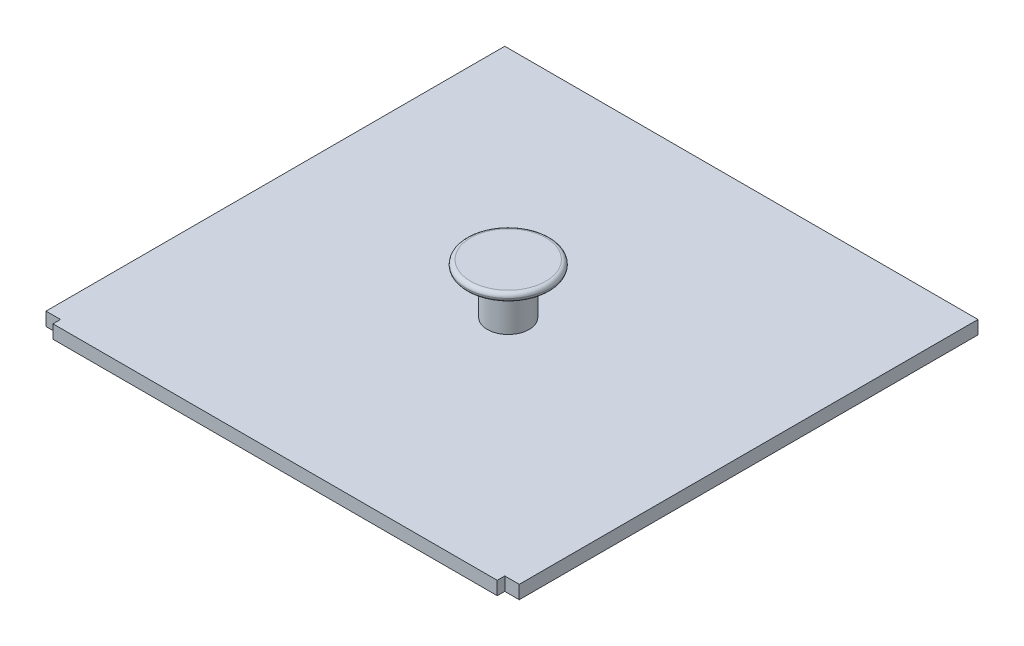
SolidWorks part; units mm, degrees
ref_plane "Ebene vorne" through (0, 0, 0) normal (0, 0, 1) x (1, 0, 0)
ref_plane "Ebene oben" through (0, 0, 0) normal (0, 1, 0) x (1, 0, 0)
ref_plane "Ebene rechts" through (0, 0, 0) normal (1, 0, 0) x (0, 0, -1)
sketch "Sketch1" plane through (0, 0, 0) normal (0, 1, 0) x (1, 0, 0)
  line L1 (-84.9, 83.65) -> (84.9, 83.65)
  line L2 (-84.9, 83.65) -> (-84.9, -83.65)
  line L3 (-84.9, -83.65) -> (84.9, -83.65)
  line L4 (84.9, 83.65) -> (84.9, -83.65)
  line L5 (-84.9, 83.65) -> (84.9, -83.65) construction
  line L6 (-84.9, -83.65) -> (84.9, 83.65) construction
  point P0 (0, 0)
  dimension "D1" = 169.8
  dimension "D2" = 167.3
extrude "Boss-Extrude1" add sketch "Sketch1" along normal mid plane 4.8
sketch "Sketch2" plane through (0, 2.4, 0) normal (0, 1, 0) x (1, 0, 0)
  line L0 (84.9, 83.65) -> (-84.9, 83.65) construction
  line L1 (0, 83.65) -> (0, -83.65) construction
  line L2 (-84.9, -83.65) -> (84.9, -83.65) construction
  circle A1 centre (0, 0) radius 7.5
  dimension "D2" = 15
  dimension "D4" = 0
extrude "Boss-Extrude2" add sketch "Sketch2" along normal blind 15
sketch "Sketch6" plane through (0, 17.4, 0) normal (0, 1, 0) x (1, 0, 0)
  circle A0 centre (0, 0) radius 15
  dimension "D1" = 30
extrude "Boss-Extrude4" add sketch "Sketch6" along normal blind 3
sketch "Sketch7" plane through (0, 2.4, 0) normal (0, 1, 0) x (1, 0, 0)
  line L1 (-84.9, -83.65) -> (-79.7, -83.65)
  line L2 (-84.9, -83.65) -> (-84.9, -80.95)
  line L3 (-84.9, -80.95) -> (-79.7, -80.95)
  line L4 (-79.7, -83.65) -> (-79.7, -80.95)
  line L5 (84.9, -83.65) -> (79.7, -83.65)
  line L6 (84.9, -83.65) -> (84.9, -80.95)
  line L7 (84.9, -80.95) -> (79.7, -80.95)
  line L8 (79.7, -83.65) -> (79.7, -80.95)
  dimension "D1" = 5.2
  dimension "D2" = 2.7
extrude "Cut-Extrude1" cut sketch "Sketch7" against normal through all
fillet "Fillet2" radius 1.5 2 edges at (0, 17.4, 15) (0, 20.4, 15)
